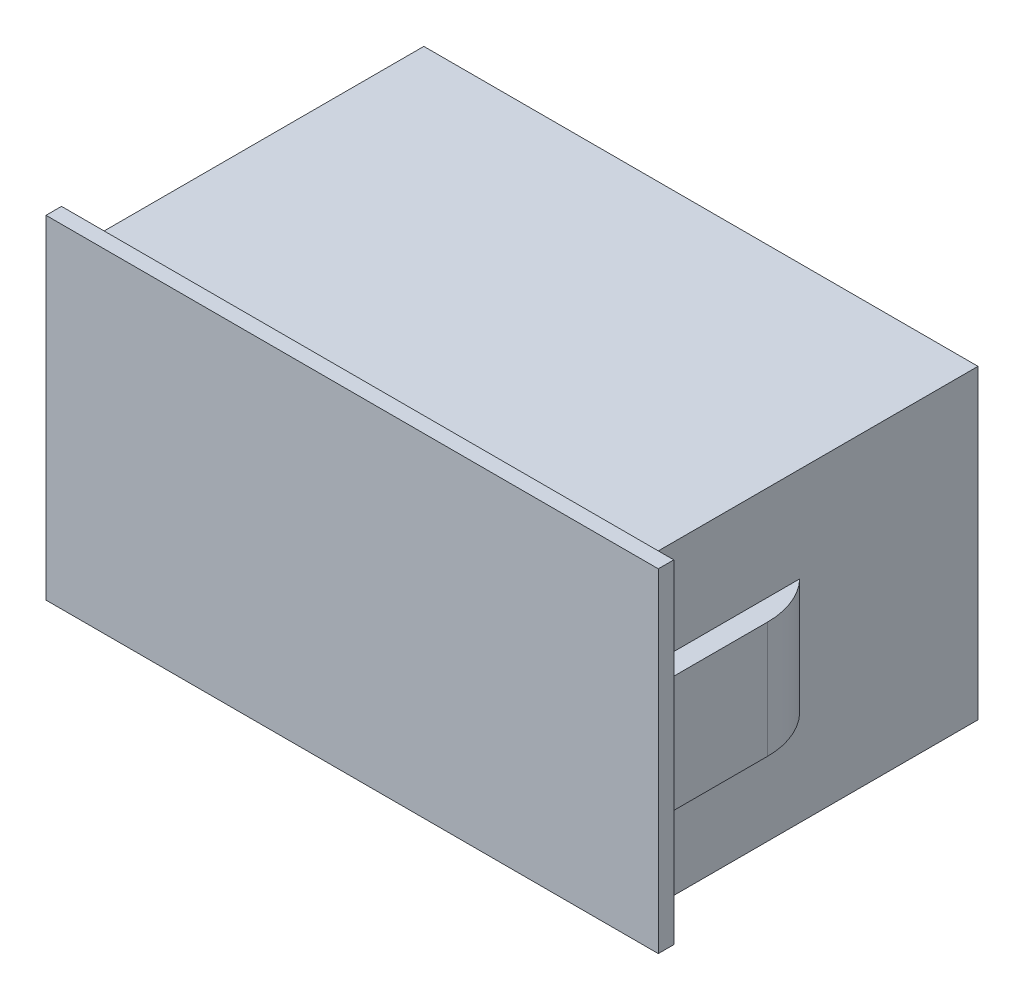
SolidWorks part; units mm, degrees
ref_plane "Ebene vorne" through (0, 0, 0) normal (0, 0, 1) x (1, 0, 0)
ref_plane "Ebene oben" through (0, 0, 0) normal (0, 1, 0) x (1, 0, 0)
ref_plane "Ebene rechts" through (0, 0, 0) normal (1, 0, 0) x (0, 0, -1)
sketch "Skizze1" plane through (0, 0, 0) normal (0, 0, 1) x (1, 0, 0)
  line L1 (-39.5, 21.5) -> (39.5, 21.5)
  line L2 (-39.5, 21.5) -> (-39.5, -21.5)
  line L3 (-39.5, -21.5) -> (39.5, -21.5)
  line L4 (39.5, 21.5) -> (39.5, -21.5)
  line L5 (-39.5, 21.5) -> (39.5, -21.5) construction
  line L6 (-39.5, -21.5) -> (39.5, 21.5) construction
  point P0 (0, 0)
  dimension "D1" = 79
  dimension "D2" = 43
extrude "Aufsatz-Linear austragen1" add sketch "Skizze1" along normal blind 45
sketch "Skizze2" plane through (0, 0, 0) normal (0, 0, -1) x (-1, 0, 0)
  line L1 (-35.75, 19.75) -> (35.75, 19.75)
  line L2 (-35.75, 19.75) -> (-35.75, -19.75)
  line L3 (-35.75, -19.75) -> (35.75, -19.75)
  line L4 (35.75, 19.75) -> (35.75, -19.75)
  line L5 (-35.75, 19.75) -> (35.75, -19.75) construction
  line L6 (-35.75, -19.75) -> (35.75, 19.75) construction
  line L7 (39.5, -21.5) -> (-39.5, -21.5)
  line L8 (39.5, -21.5) -> (39.5, 21.5)
  line L9 (39.5, 21.5) -> (-39.5, 21.5)
  line L10 (-39.5, -21.5) -> (-39.5, 21.5)
  line L11 (39.5, -21.5) -> (-39.5, 21.5) construction
  line L12 (39.5, 21.5) -> (-39.5, -21.5) construction
  point P0 (0, 0)
  point P6 (0, 0)
  dimension "D1" = 71.5
  dimension "D2" = 39.5
extrude "Schnitt-Linear austragen1" cut sketch "Skizze2" against normal offset from surface (43 mm away) 2 up to face at (0, 0, 45)
sketch "Skizze3" plane through (0, 0, 43) normal (0, 0, -1) x (-1, 0, 0)
  line L0 (37.125, 0) -> (-37.125, 0) construction
  line L1 (-35.75, 19.75) -> (-35.75, -19.75) construction
  line L2 (-38.5, 7.5) -> (-35.75, 7.5)
  line L3 (-38.5, 7.5) -> (-38.5, -7.5)
  line L4 (-38.5, -7.5) -> (-35.75, -7.5)
  line L5 (-35.75, 7.5) -> (-35.75, -7.5)
  line L6 (-38.5, 7.5) -> (-35.75, -7.5) construction
  line L7 (-38.5, -7.5) -> (-35.75, 7.5) construction
  line L8 (35.75, -19.75) -> (35.75, 19.75) construction
  line L9 (38.5, -7.5) -> (35.75, -7.5)
  line L10 (38.5, -7.5) -> (38.5, 7.5)
  line L11 (38.5, 7.5) -> (35.75, 7.5)
  line L12 (35.75, -7.5) -> (35.75, 7.5)
  line L13 (38.5, -7.5) -> (35.75, 7.5) construction
  line L14 (38.5, 7.5) -> (35.75, -7.5) construction
  point P3 (0, 0)
  dimension "D1" = 77
  dimension "D2" = 15
extrude "Aufsatz-Linear austragen2" add sketch "Skizze3" along normal blind 20
fillet "Verrundung1" radius 10 2 edges at (-38.5, 0, 23) (38.5, 0, 23)
